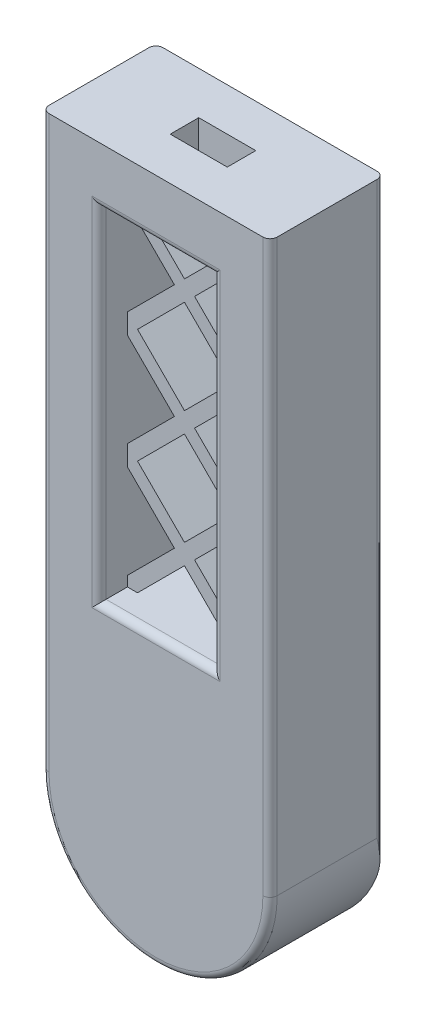
SolidWorks part; units mm, degrees
ref_plane "Płaszczyzna przednia" through (0, 0, 0) normal (0, 0, 1) x (1, 0, 0)
ref_plane "Płaszczyzna górna" through (0, 0, 0) normal (0, 1, 0) x (1, 0, 0)
ref_plane "Płaszczyzna prawa" through (0, 0, 0) normal (1, 0, 0) x (0, 0, -1)
sketch "Sketch1" plane through (0, 0, 0) normal (0, 0, 1) x (1, 0, 0)
  line L0 (0, 0) -> (40, 0)
  line L1 (40, 0) -> (40, -100)
  line L2 (0, 0) -> (0, -100)
  line L4 (10, -10) -> (10, -70)
  line L5 (10, -10) -> (30, -10)
  line L6 (30, -10) -> (30, -70)
  line L7 (10, -10) -> (10, -100) construction
  line L8 (30, -10) -> (30, -100) construction
  line L9 (10, -70) -> (30, -70)
  line L10 (20, -80) -> (30, -80) construction
  arc A0 (0, -100) -> (40, -100) centre (20, -100) ccw
  circle A1 centre (20, -100) radius 10
  dimension "D5" = 20
  dimension "D7" = 20
  dimension "D1" = 40
  dimension "D2" = 100
  dimension "D4" = 10
  dimension "D6" = 20
  dimension "D3" = 10
extrude "Boss-Extrude1" add sketch "Sketch1" along normal mid plane 20
extrude "Boss-Extrude2" add sketch "Sketch1<3>" against normal blind 5 and the other way blind 10 contours A1 region at (20, -100, 0)
sketch "Sketch1<3>" plane through (0, 0, 0) normal (0, 0, 1) x (1, 0, 0) same geometry as "Sketch1"
sketch "Sketch3" plane through (0, 0, 0) normal (0, 1, 0) x (1, 0, 0)
  line L0 (0, 10) -> (40, -10) construction
  line L1 (0, -10) -> (40, 10) construction
  line L3 (15, 2.5) -> (25, 2.5)
  line L4 (15, 2.5) -> (15, -2.5)
  line L5 (15, -2.5) -> (25, -2.5)
  line L6 (25, 2.5) -> (25, -2.5)
  line L7 (15, 2.5) -> (25, -2.5) construction
  line L8 (15, -2.5) -> (25, 2.5) construction
  point P8 (20, 0)
  dimension "D1" = 10
  dimension "D2" = 5
extrude "Cut-Extrude1" cut sketch "Sketch3" against normal blind 5
sketch "Sketch4" plane through (0, 0, 0) normal (0, 0, 1) x (1, 0, 0)
  line L0 (11.7678, -10) -> (31.7678, -30)
  line L1 (30, -10) -> (10, -10) construction
  line L2 (10, -48.2322) -> (10, -51.7678)
  line L3 (10, -11.7678) -> (28.2322, -30)
  line L4 (10, -10) -> (10, -70) construction
  line L5 (11.7678, -10) -> (10, -10) construction
  line L6 (10, -10) -> (10, -11.7678) construction
  line L7 (30, -28.2322) -> (30, -31.7678)
  line L8 (28.2322, -30) -> (8.2322, -50)
  line L9 (31.7678, -30) -> (11.7678, -50)
  line L10 (11.7678, -50) -> (30, -68.2322)
  line L11 (28.2322, -30) -> (31.7678, -30) construction
  line L12 (30, -70) -> (30, -10) construction
  line L13 (8.2322, -50) -> (11.7678, -50) construction
  line L14 (8.2322, -50) -> (28.2322, -70)
  line L15 (28.2322, -70) -> (30, -70) construction
  line L16 (10, -70) -> (30, -70) construction
  line L17 (30, -70) -> (30, -68.2322) construction
  line L18 (11.7678, -10) -> (10, -10)
  line L19 (10, -10) -> (10, -11.7678)
  line L20 (28.2322, -70) -> (30, -70)
  line L21 (30, -70) -> (30, -68.2322)
  line L22 (20, -10) -> (20, -70) construction
  line L23 (11.7678, -70) -> (10, -70)
  line L24 (31.7678, -50) -> (11.7678, -70)
  line L25 (11.7678, -30) -> (31.7678, -50)
  line L26 (30, -11.7678) -> (11.7678, -30)
  line L27 (30, -10) -> (30, -11.7678)
  line L28 (28.2322, -10) -> (30, -10)
  line L29 (28.2322, -10) -> (8.2322, -30)
  line L30 (8.2322, -30) -> (28.2322, -50)
  line L31 (28.2322, -50) -> (10, -68.2322)
  line L32 (10, -70) -> (10, -68.2322)
  point P13 (30, -30)
  point P19 (10, -50)
  dimension "D1" = 2.5
  dimension "D2" = 45
  dimension "D3" = 28.2843
  dimension "D4" = 2.5
  dimension "D5" = 3.5355
extrude "Boss-Extrude3" add sketch "Sketch4" along normal mid plane 10 contours L20 L21 L10 L9 L7 L0 L18 L19 L3 L8 L2 L14 | L23 L32 L31 L30 L29 L28 L27 L26 L25 L24 | L21 L10 L9 L0 L18 L19 L3 L8 L14 L20 region at (25.2247, -65.2247, 0)
fillet "Fillet1" radius 1.25 13 edges at (20, -120, 10) (0, -50, 10) (0, -50, -10) (40, -50, -10) (20, -10, -10) (10, -40, -10) (20, -70, -10) (30, -40, -10) (20, -70, 10) (30, -40, 10) (20, -10, 10) (10, -40, 10) (40, -50, 10) tangent propagation no
